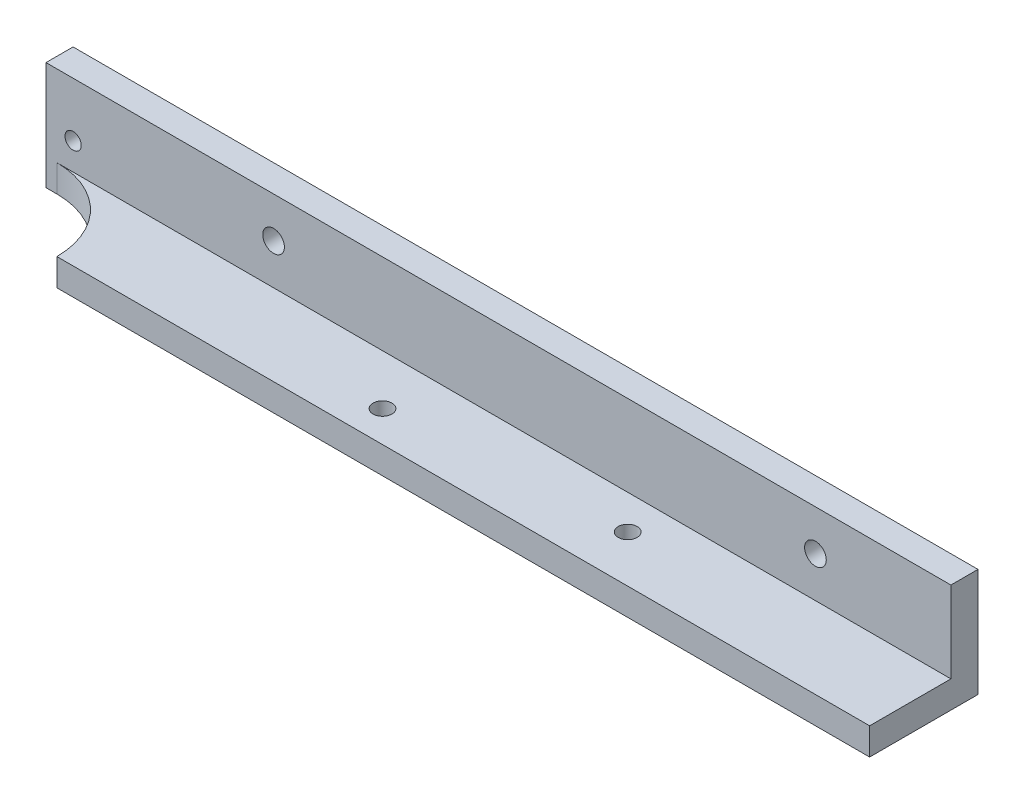
SolidWorks part; units mm, degrees
material "PET"
ref_plane "Front Plane" through (0, 0, 0) normal (0, 0, 1) x (1, 0, 0)
ref_plane "Top Plane" through (0, 0, 0) normal (0, 1, 0) x (1, 0, 0)
ref_plane "Right Plane" through (0, 0, 0) normal (1, 0, 0) x (0, 0, -1)
sketch "Sketch1" plane through (0, 0, 0) normal (0, 1, 0) x (1, 0, 0)
  line L1 (0, 0) -> (150, 0)
  line L2 (0, 0) -> (0, 20)
  line L3 (0, 20) -> (150, 20)
  line L4 (150, 0) -> (150, 20)
  dimension "D1" = 150
  dimension "D2" = 20
extrude "Boss-Extrude1" add sketch "Sketch1" against normal blind 5
sketch "Sketch3" plane through (0, 0, 0) normal (0, 1, 0) x (1, 0, 0)
  line L0 (150, 0) -> (150, 20) construction
  line L1 (0, 20) -> (150, 20)
  line L2 (0, 20) -> (0, 15)
  line L3 (0, 15) -> (150, 15)
  line L4 (150, 20) -> (150, 15)
  dimension "D1" = 5
extrude "Boss-Extrude2" add sketch "Sketch3" along normal blind 15
sketch "Sketch5" plane through (0, 0, -15) normal (0, 0, 1) x (1, 0, 0)
  line L0 (0, 15) -> (0, 0) construction
  line L1 (150, 15) -> (150, 0) construction
  line L2 (0, 0) -> (150, 0) construction
  circle A0 centre (25, 7.5) radius 2
  circle A1 centre (125, 7.5) radius 2
  dimension "D1" = 4
  dimension "D2" = 4
  dimension "D3" = 25
  dimension "D4" = 25
  dimension "D5" = 7.5
  dimension "D6" = 7.5
extrude "Cut-Extrude1" cut sketch "Sketch5" against normal through all
sketch "Sketch6" plane through (0, 0, 0) normal (0, 1, 0) x (1, 0, 0)
  line L0 (0, 15) -> (0, 0) construction
  line L1 (0, 0) -> (150, 0) construction
  circle A0 centre (54.35, 5.75) radius 1.75
  circle A1 centre (96.7, 8.65) radius 1.75
  dimension "D1" = 3.5
  dimension "D2" = 3.5
  dimension "D3" = 54.35
  dimension "D4" = 42.35
  dimension "D5" = 5.75
  dimension "D6" = 8.65
extrude "Cut-Extrude2" cut sketch "Sketch6" against normal through all
sketch "Sketch7" plane through (0, 0, 0) normal (-1, 0, 0) x (0, 0, 1)
  line L0 (-20, -5) -> (0, -5) construction
  line L1 (-20, 15) -> (-15, 15)
  line L2 (-20, 15) -> (-20, -5)
  line L3 (-20, -5) -> (-15, -5)
  line L4 (-15, 15) -> (-15, -5)
extrude "Boss-Extrude3" add sketch "Sketch7" along normal blind 17
sketch "Sketch8" plane through (0, 0, -15) normal (0, 0, 1) x (1, 0, 0)
  line L0 (-17, 15) -> (150, 15) construction
  line L1 (-17, -5) -> (-17, 15) construction
  circle A0 centre (-12, 5) radius 1.5
  dimension "D3" = 3
  dimension "D1" = 10
  dimension "D2" = 5
extrude "Cut-Extrude3" cut sketch "Sketch8" against normal through all
fillet "Fillet2" radius 15 1 edges at (0, -2.5, -15) type face fillet first side face at (0, -2.5, -7.5) second side face at (-10.5, 5, -15)
